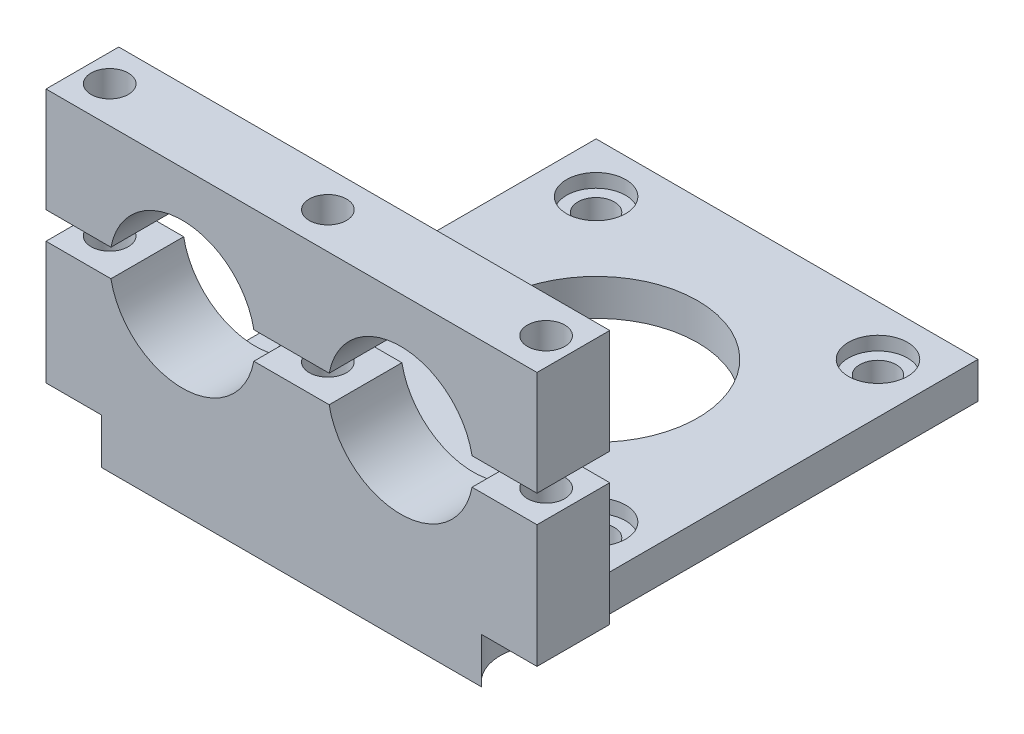
SolidWorks part; units mm, degrees
ref_plane "Front Plane" through (0, 0, 0) normal (0, 0, 1) x (1, 0, 0)
ref_plane "Top Plane" through (0, 0, 0) normal (0, 1, 0) x (1, 0, 0)
ref_plane "Right Plane" through (0, 0, 0) normal (1, 0, 0) x (0, 0, -1)
sketch "Sketch1" plane through (0, 0, 0) normal (0, 1, 0) x (1, 0, 0)
  line L0 (-13.0363, -24.1159) -> (-13.0363, -32.1159)
  line L1 (-13.0363, 22.3841) -> (28.9637, 22.3841)
  line L2 (-13.0363, 22.3841) -> (-13.0363, -24.1159)
  line L3 (-13.0363, -24.1159) -> (28.9637, -24.1159)
  line L4 (28.9637, 22.3841) -> (28.9637, -24.1159)
  line L5 (-13.0363, -32.1159) -> (28.9637, -32.1159)
  line L6 (28.9637, -32.1159) -> (28.9637, -24.1159)
  line L7 (-13.0363, -32.1159) -> (-19.0363, -32.1159)
  line L8 (-19.0363, -32.1159) -> (-19.0363, -24.1159)
  line L9 (-7.5363, -14.1159) -> (-7.5363, 16.8841) construction
  line L10 (-7.5363, -14.1159) -> (23.4637, -14.1159) construction
  line L11 (-19.0363, -24.1159) -> (-13.0363, -24.1159)
  line L12 (28.9637, -24.1159) -> (34.9637, -24.1159)
  line L13 (34.9637, -24.1159) -> (34.9637, -32.1159)
  line L14 (34.9637, -32.1159) -> (28.9637, -32.1159)
  line L15 (7.9637, -14.1159) -> (7.9637, 1.3841) construction
  line L16 (-7.5363, 1.3841) -> (7.9637, 1.3841) construction
  circle A0 centre (-7.5363, 16.8841) radius 2
  circle A1 centre (23.4637, 16.8841) radius 2
  circle A2 centre (23.4637, -14.1159) radius 2
  circle A3 centre (-7.5363, -14.1159) radius 2
  circle A4 centre (7.9637, 1.3841) radius 11.175
  circle A5 centre (23.4637, -14.1159) radius 3.25
  circle A6 centre (23.4637, 16.8841) radius 3.25
  circle A7 centre (-7.5363, -14.1159) radius 3.25
  circle A8 centre (-7.5363, 16.8841) radius 3.25
  dimension "D7" = 4
  dimension "D8" = 4
  dimension "D9" = 4
  dimension "D10" = 4
  dimension "D16" = 22.35
  dimension "D17" = 6.5
  dimension "D18" = 6.5
  dimension "D19" = 6.5
  dimension "D20" = 6.5
  dimension "D1" = 42
  dimension "D3" = 31
  dimension "D4" = 31
  dimension "D5" = 31
  dimension "D6" = 31
  dimension "D11" = 10
  dimension "D12" = 5.5
  dimension "D13" = 8
  dimension "D14" = 6
  dimension "D15" = 6
  dimension "D2" = 5.5
extrude "Boss-Extrude1" add sketch "Sketch1" along normal blind 5 contours L4 L1 L2 L3 A3 A2 A1 A0 | L5 L3 L0 | L5 L6 L3 region at (7.9637, 0, 28.1159) region at (-12.4097, 0, 0.8659)
extrude "Boss-Extrude2" add sketch "Sketch1<3>" along normal blind 30 from surface contours L5 L6 L3 | L5 L3 L0 region at (7.9637, 0, 28.1159) starting at face at (-7.5363, 5, -13.6341)
sketch "Sketch1<3>" plane through (0, 0, 0) normal (0, 1, 0) x (1, 0, 0) same geometry as "Sketch1"
sketch "Sketch2" plane through (0, 0, 24.1159) normal (0, 0, -1) x (-1, 0, 0)
  line L0 (-28.9637, 20) -> (13.0363, 20) construction
  line L1 (-28.9637, 35) -> (-28.9637, 5) construction
  line L2 (13.0363, 35) -> (13.0363, 5) construction
  line L3 (-28.9637, 20) -> (-28.9637, 21.5)
  line L4 (-28.9637, 21.5) -> (13.0363, 21.5)
  line L5 (13.0363, 21.5) -> (13.0363, 20)
  line L6 (13.0363, 20) -> (13.0363, 18.5)
  line L7 (13.0363, 18.5) -> (-28.9637, 18.5)
  line L8 (-28.9637, 18.5) -> (-28.9637, 20)
  circle A0 centre (4.0363, 20) radius 8
  circle A1 centre (-19.9637, 20) radius 8
  dimension "D3" = 16
  dimension "D4" = 16
  dimension "D1" = 9
  dimension "D2" = 9
  dimension "D5" = 1.5
  dimension "D6" = 1.5
extrude "Cut-Extrude1" cut sketch "Sketch2" against normal through all contours L4 A0 | L7 A0 | L7 A1 | L4 A1 | L4 L5 L6 L7 L8 L3 region at (19.9637, 24.2192, 24.1159) region at (19.9637, 15.7808, 24.1159) region at (-4.0363, 24.2192, 24.1159) region at (-4.0363, 15.7808, 24.1159)
sketch "Sketch3" plane through (0, 35, 0) normal (0, 1, 0) x (1, 0, 0)
  line L0 (-13.0363, -28.1159) -> (28.9637, -28.1159) construction
  line L1 (7.9637, -24.1159) -> (7.9637, -32.1159) construction
  line L4 (28.9637, -24.1159) -> (-13.0363, -24.1159)
  line L5 (-13.0363, -24.1159) -> (-13.0363, -32.1159)
  line L6 (-13.0363, -32.1159) -> (28.9637, -32.1159)
  line L7 (28.9637, -32.1159) -> (28.9637, -24.1159)
  line L8 (28.9637, -24.1159) -> (-13.0363, -24.1159)
  line L9 (-13.0363, -24.1159) -> (-13.0363, -32.1159)
  line L10 (-13.0363, -32.1159) -> (28.9637, -32.1159)
  line L11 (28.9637, -32.1159) -> (28.9637, -24.1159)
  circle A0 centre (7.9637, -28.1159) radius 2.05
  dimension "D2" = 4.1
  dimension "D1" = 0
extrude "Cut-Extrude3" cut sketch "Sketch3" against normal through all contours A0
extrude "Boss-Extrude3" add sketch "Sketch1<4>" along normal up to surface (18.5 mm away) contours L14 L13 L12 L6 | L11 L8 L7 L0 region at (-16.0363, 0, 28.1159) region at (31.9637, 0, 28.1159) up to face at (-12.4654, 18.5, 28.1159)
sketch "Sketch1<4>" plane through (0, 0, 0) normal (0, 1, 0) x (1, 0, 0) same geometry as "Sketch1"
sketch "Sketch4" plane through (0, 18.5, 0) normal (0, 1, 0) x (1, 0, 0)
  line L0 (-11.8944, -32.1159) -> (-11.8944, -24.1159) construction
  line L1 (-11.8944, -24.1159) -> (-19.0363, -24.1159) construction
  line L2 (-19.0363, -24.1159) -> (-19.0363, -32.1159) construction
  line L3 (-19.0363, -32.1159) -> (-11.8944, -32.1159) construction
  line L4 (27.8218, -24.1159) -> (27.8218, -32.1159) construction
  line L5 (27.8218, -32.1159) -> (34.9637, -32.1159) construction
  line L6 (34.9637, -32.1159) -> (34.9637, -24.1159) construction
  line L7 (34.9637, -24.1159) -> (27.8218, -24.1159) construction
  line L8 (-11.8944, -32.1159) -> (-11.8944, -24.1159)
  line L9 (-11.8944, -24.1159) -> (-19.0363, -24.1159)
  line L10 (-19.0363, -24.1159) -> (-19.0363, -32.1159)
  line L11 (-19.0363, -32.1159) -> (-11.8944, -32.1159)
  line L12 (27.8218, -24.1159) -> (27.8218, -32.1159)
  line L13 (27.8218, -32.1159) -> (34.9637, -32.1159)
  line L14 (34.9637, -32.1159) -> (34.9637, -24.1159)
  line L15 (34.9637, -24.1159) -> (27.8218, -24.1159)
  line L16 (-19.0363, -28.1159) -> (34.9637, -28.1159) construction
  line L17 (31.9637, -32.1159) -> (31.9637, -24.1159) construction
  line L18 (-16.0363, -32.1159) -> (-16.0363, -24.1159) construction
  line L19 (-19.0363, -24.1159) -> (-11.8944, -24.1159) construction
  circle A0 centre (-16.0363, -28.1159) radius 2.05
  circle A1 centre (31.9637, -28.1159) radius 2.05
  dimension "D1" = 4.1
  dimension "D2" = 4.1
  dimension "D3" = 3
  dimension "D4" = 3
extrude "Cut-Extrude4" cut sketch "Sketch4" against normal through all contours A0 | A1 region at (-16.0363, 18.5, 28.1159) region at (31.9637, 18.5, 28.1159)
sketch "Sketch5" plane through (0, 35, 0) normal (0, 1, 0) x (1, 0, 0)
  line L0 (-11.8944, -32.1159) -> (-11.8944, -24.1159) construction
  line L1 (-11.8944, -24.1159) -> (-19.0363, -24.1159) construction
  line L2 (-19.0363, -24.1159) -> (-19.0363, -32.1159) construction
  line L3 (-19.0363, -32.1159) -> (-11.8944, -32.1159) construction
  line L4 (27.8218, -24.1159) -> (27.8218, -32.1159) construction
  line L5 (27.8218, -32.1159) -> (34.9637, -32.1159) construction
  line L6 (34.9637, -32.1159) -> (34.9637, -24.1159) construction
  line L7 (34.9637, -24.1159) -> (27.8218, -24.1159) construction
  line L8 (-11.8944, -32.1159) -> (-11.8944, -24.1159)
  line L9 (-11.8944, -24.1159) -> (-19.0363, -24.1159)
  line L10 (-19.0363, -24.1159) -> (-19.0363, -32.1159)
  line L11 (-19.0363, -32.1159) -> (-11.8944, -32.1159)
  line L12 (27.8218, -24.1159) -> (27.8218, -32.1159)
  line L13 (27.8218, -32.1159) -> (34.9637, -32.1159)
  line L14 (34.9637, -32.1159) -> (34.9637, -24.1159)
  line L15 (34.9637, -24.1159) -> (27.8218, -24.1159)
  circle A0 centre (-16.0363, -28.1159) radius 2.05 construction
  circle A1 centre (31.9637, -28.1159) radius 2.05 construction
  circle A2 centre (-16.0363, -28.1159) radius 2.05
  circle A3 centre (31.9637, -28.1159) radius 2.05
extrude "Boss-Extrude4" add sketch "Sketch5" against normal up to surface (13.5 mm away) up to face at (28.3927, 21.5, 28.1159)
sketch "Sketch6" plane through (0, 35, 0) normal (0, 1, 0) x (1, 0, 0)
  line L4 (-19.0363, -24.1159) -> (-19.0363, -32.1159)
  line L5 (-19.0363, -32.1159) -> (34.9637, -32.1159)
  line L6 (34.9637, -32.1159) -> (34.9637, -24.1159)
  line L7 (34.9637, -24.1159) -> (-19.0363, -24.1159)
  line L8 (-19.0363, -24.1159) -> (-19.0363, -32.1159)
  line L9 (-19.0363, -32.1159) -> (34.9637, -32.1159)
  line L10 (34.9637, -32.1159) -> (34.9637, -24.1159)
  line L11 (34.9637, -24.1159) -> (-19.0363, -24.1159)
  dimension "D1" = 0
extrude "Cut-Extrude5" cut sketch "Sketch6" against normal blind 5
sketch "Sketch7" plane through (0, 0, 0) normal (0, -1, 0) x (1, 0, 0)
  line L24 (-13.0363, 24.1159) -> (-13.0363, 32.1159)
  line L29 (28.9637, 32.1159) -> (28.9637, 24.1159)
  line L30 (-13.0363, 32.1159) -> (-19.0363, 32.1159)
  line L47 (28.9637, -22.3841) -> (28.9637, 24.1159)
  line L48 (28.9637, 24.1159) -> (34.9637, 24.1159)
  line L49 (34.9637, 24.1159) -> (34.9637, 32.1159)
  line L50 (34.9637, 32.1159) -> (-19.0363, 32.1159)
  line L51 (-19.0363, 32.1159) -> (-19.0363, 24.1159)
  line L52 (-19.0363, 24.1159) -> (-13.0363, 24.1159)
  line L53 (-19.0363, 24.1159) -> (-13.0363, 24.1159)
  line L54 (-13.0363, 24.1159) -> (-13.0363, -22.3841)
  line L56 (28.9637, 24.1159) -> (34.9637, 24.1159)
  line L57 (34.9637, 24.1159) -> (34.9637, 32.1159)
  line L58 (34.9637, 32.1159) -> (28.9637, 32.1159)
  line L59 (-19.0363, 32.1159) -> (-19.0363, 24.1159)
  line L61 (-13.0363, -22.3841) -> (28.9637, -22.3841)
  dimension "D1" = 0
extrude "Cut-Extrude8" cut sketch "Sketch7" against normal blind 5
sketch "Sketch8" plane through (0, 0, 0) normal (0, -1, 0) x (1, 0, 0)
  circle A0 centre (31.9637, 28.1159) radius 2.05 construction
  circle A1 centre (-16.0363, 28.1159) radius 2.05 construction
  circle A2 centre (31.9637, 28.1159) radius 2.05
  circle A3 centre (-16.0363, 28.1159) radius 2.05
  circle A4 centre (-16.0363, 28.1159) radius 5.05
  circle A5 centre (31.9637, 28.1159) radius 5.05
  dimension "D1" = 3
extrude "Cut-Extrude9" cut sketch "Sketch8" against normal blind 5
sketch "Sketch9" plane through (0, 5, 0) normal (0, 1, 0) x (1, 0, 0)
  line L4 (-12.9537, -24.1159) -> (28.8811, -24.1159)
  line L5 (28.9637, -24.0536) -> (28.9637, 22.3841)
  line L6 (28.9637, 22.3841) -> (-13.0363, 22.3841)
  line L7 (-13.0363, 22.3841) -> (-13.0363, -24.0536)
  line L8 (-12.9537, -24.1159) -> (28.8811, -24.1159)
  line L9 (28.9637, -24.0536) -> (28.9637, 22.3841)
  line L10 (28.9637, 22.3841) -> (-13.0363, 22.3841)
  line L11 (-13.0363, 22.3841) -> (-13.0363, -24.0536)
  arc A1 (-12.9537, -24.1159) -> (-13.0363, -24.0536) centre (-16.0363, -28.1159) ccw
  arc A2 (-12.9537, -24.1159) -> (-13.0363, -24.0536) centre (-16.0363, -28.1159) ccw
  arc A4 (28.9637, -24.0536) -> (28.8811, -24.1159) centre (31.9637, -28.1159) ccw
  arc A5 (28.9637, -24.0536) -> (28.8811, -24.1159) centre (31.9637, -28.1159) ccw
  dimension "D1" = 0
extrude "Cut-Extrude10" cut sketch "Sketch9" against normal blind 1
sketch "Sketch10" plane through (0, 30, 0) normal (0, 1, 0) x (1, 0, 0)
  line L4 (34.9637, -24.1159) -> (-19.0363, -24.1159)
  line L5 (-19.0363, -24.1159) -> (-19.0363, -32.1159)
  line L6 (-19.0363, -32.1159) -> (34.9637, -32.1159)
  line L7 (34.9637, -32.1159) -> (34.9637, -24.1159)
  line L8 (34.9637, -24.1159) -> (-19.0363, -24.1159)
  line L9 (-19.0363, -24.1159) -> (-19.0363, -32.1159)
  line L10 (-19.0363, -32.1159) -> (34.9637, -32.1159)
  line L11 (34.9637, -32.1159) -> (34.9637, -24.1159)
  circle A0 centre (31.9637, -28.1159) radius 2.05 construction
  circle A1 centre (7.9637, -28.1159) radius 2.05 construction
  circle A2 centre (-16.0363, -28.1159) radius 2.05 construction
  circle A3 centre (31.9637, -28.1159) radius 2.05
  circle A4 centre (7.9637, -28.1159) radius 2.05
  circle A5 centre (-16.0363, -28.1159) radius 2.05
  dimension "D1" = 0
extrude "Boss-Extrude5" add sketch "Sketch10" along normal blind 3
extrude "Boss-Extrude6" add sketch "Sketch1<5>" along normal blind 2.5 contours A6 A1 | A5 A2 | A8 A0 | A7 A3 region at (20.3056, 0, 14.1159) region at (20.3056, 0, -16.8841) region at (-10.6944, 0, 14.1159) region at (-10.6944, 0, -16.8841)
sketch "Sketch1<5>" plane through (0, 0, 0) normal (0, 1, 0) x (1, 0, 0) same geometry as "Sketch1"
equation "\"D8@Sketch1\"=\"D7@Sketch1\""
equation "\"D9@Sketch1\"=\"D7@Sketch1\""
equation "\"D10@Sketch1\"=\"D7@Sketch1\""
equation "\"D12@Sketch1\"=(\"D1@Sketch1\"-\"D5@Sketch1\")/2"
equation "\"D1@Sketch2\"=\"D2@Sketch2\""
equation "\"D4@Sketch2\"=\"D3@Sketch2\""
equation "\"D6@Sketch2\"=\"D5@Sketch2\""
equation "\"D15@Sketch1\"=\"D14@Sketch1\""
equation "\"D18@Sketch1\"=\"D17@Sketch1\""
equation "\"D19@Sketch1\"=\"D17@Sketch1\""
equation "\"D20@Sketch1\"=\"D17@Sketch1\""
